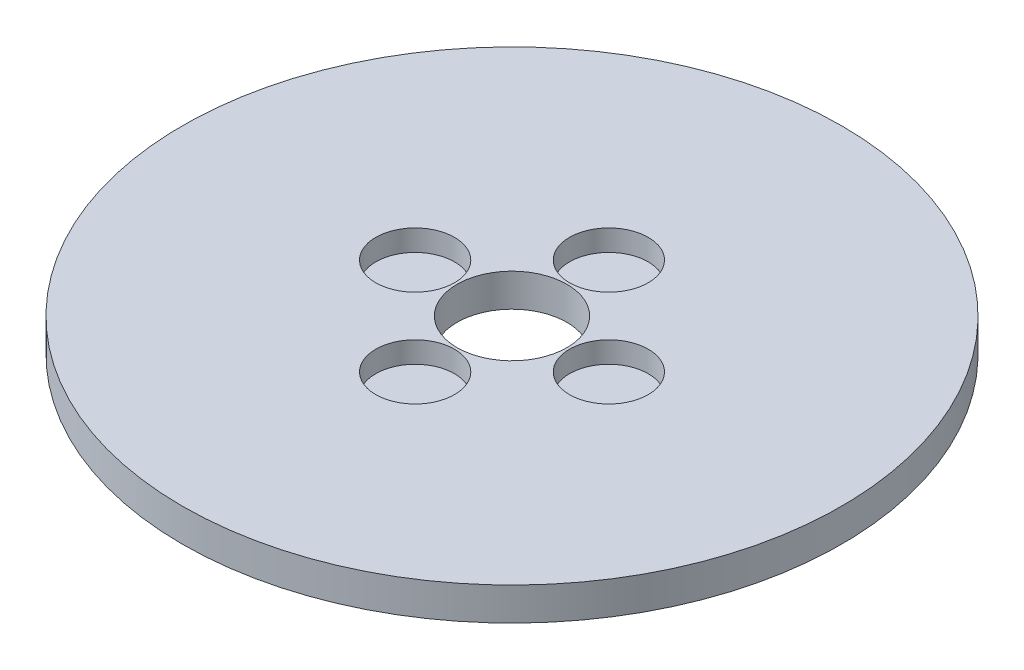
SolidWorks part; units mm, degrees
ref_plane "Front Plane" through (0, 0, 0) normal (0, 0, 1) x (1, 0, 0)
ref_plane "Top Plane" through (0, 0, 0) normal (0, 1, 0) x (1, 0, 0)
ref_plane "Right Plane" through (0, 0, 0) normal (1, 0, 0) x (0, 0, -1)
sketch "Sketch1" plane through (0, 0, 0) normal (0, 1, 0) x (1, 0, 0)
  circle A0 centre (0, 0) radius 60
  dimension "FLANGE_OD" = 120
extrude "Boss-Extrude1" add sketch "Sketch1" along normal blind 6
sketch "Sketch2" plane through (0, 0, 0) normal (0, 1, 0) x (1, 0, 0)
  circle A0 centre (0, 0) radius 10
  dimension "BORE_D" = 20
extrude "Cut-Extrude1" cut sketch "Sketch2" along normal through all
sketch "Sketch3" plane through (0, 6, 0) normal (0, 1, 0) x (1, 0, 0)
  circle A0 centre (0, 0) radius 17.6348 construction
  circle A1 centre (-17.6348, 0) radius 7.1671
  dimension "BOLT_D" = 14.3343
  dimension "BOLT_PCD" = 35.2697
extrude "Cut-Extrude2" cut sketch "Sketch3" against normal blind 3.8661
pattern_circular "CirPattern1" count 4 over 360 about axis through (0, 0, 0) along (0, 1, 0) of "Cut-Extrude2"
